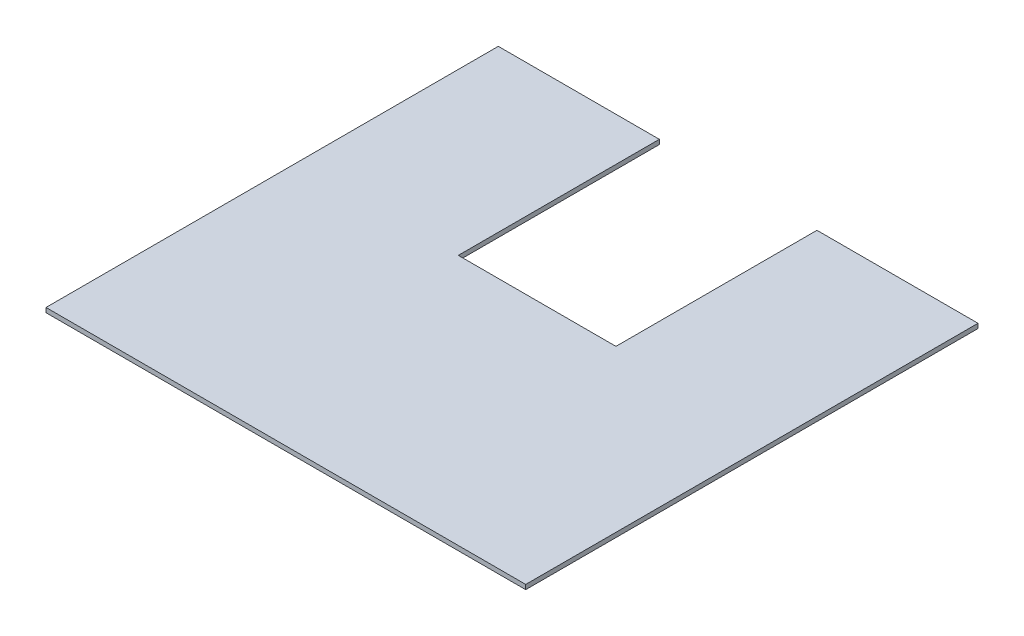
SolidWorks part; units mm, degrees
ref_plane "Front Plane" through (0, 0, 0) normal (0, 0, 1) x (1, 0, 0)
ref_plane "Top Plane" through (0, 0, 0) normal (0, 1, 0) x (1, 0, 0)
ref_plane "Right Plane" through (0, 0, 0) normal (1, 0, 0) x (0, 0, -1)
sketch "Sketch1" plane through (0, 0, 0) normal (0, 1, 0) x (1, 0, 0)
  line L1 (-105, -99) -> (105, -99)
  line L2 (-105, -99) -> (-105, 99)
  line L3 (-105, 99) -> (105, 99)
  line L4 (105, -99) -> (105, 99)
  line L5 (-105, -99) -> (105, 99) construction
  line L6 (-105, 99) -> (105, -99) construction
  point P0 (0, 0)
  dimension "D1" = 210
  dimension "D2" = 198
extrude "Boss-Extrude1" add sketch "Sketch1" along normal mid plane 2
sketch "Sketch2" plane through (0, 1, 0) normal (0, 1, 0) x (1, 0, 0)
  line L0 (105, 99) -> (-105, 99) construction
  line L1 (-34.5, 11) -> (34.5, 11)
  line L2 (-34.5, 11) -> (-34.5, 99)
  line L3 (-34.5, 99) -> (34.5, 99)
  line L4 (34.5, 11) -> (34.5, 99)
  line L5 (-34.5, 11) -> (34.5, 99) construction
  line L6 (-34.5, 99) -> (34.5, 11) construction
  point P0 (0, 55)
  dimension "D1" = 69
  dimension "D2" = 88
extrude "Cut-Extrude1" cut sketch "Sketch2" against normal through all
